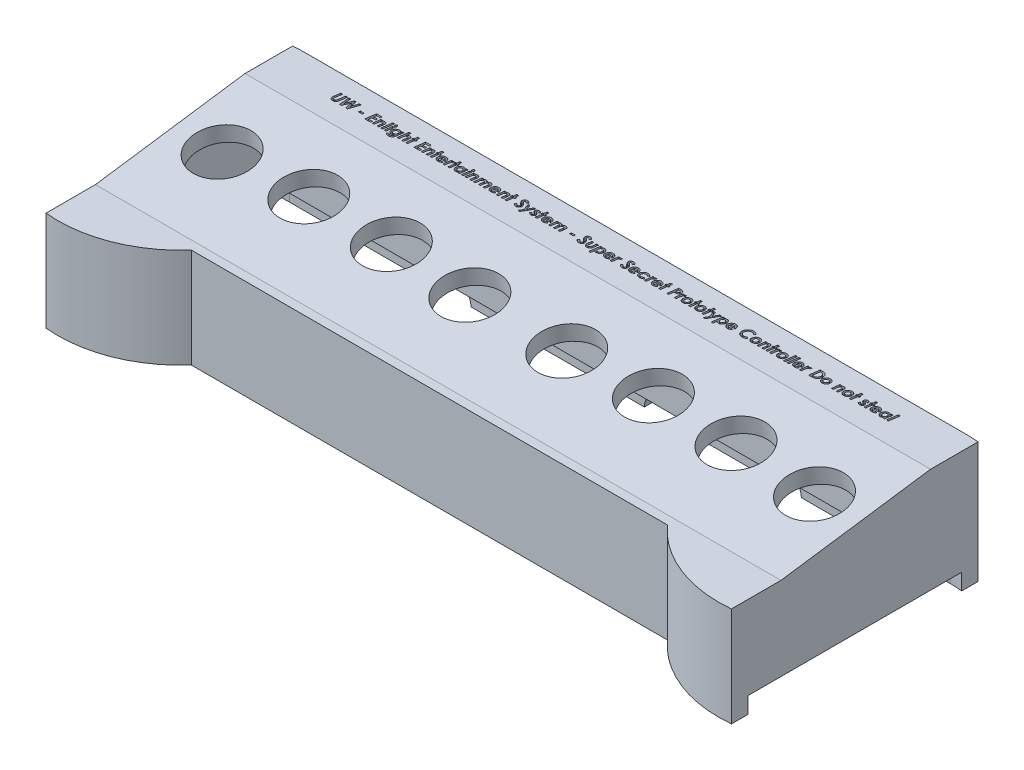
SolidWorks part; units mm, degrees
ref_plane "Front Plane" through (0, 0, 0) normal (0, 0, 1) x (1, 0, 0)
ref_plane "Top Plane" through (0, 0, 0) normal (0, 1, 0) x (1, 0, 0)
ref_plane "Right Plane" through (0, 0, 0) normal (1, 0, 0) x (0, 0, -1)
sketch "Sketch1" plane through (0, 0, 0) normal (0, 1, 0) x (1, 0, 0)
  line L3 (161.7, 30.2918) -> (-41.5, 30.2918)
  line L7 (-13.1019, -33.2082) -> (133.3019, -33.2082)
  line L8 (-63.3461, -39.0229) -> (-76.3578, -44.5347) construction
  line L9 (-41.5, -7.8082) -> (-79.6, -7.8082) construction
  line L10 (161.7, -7.8082) -> (199.8, -7.8082) construction
  arc A0 (-41.5, 30.2918) -> (-13.1019, -33.2082) centre (-41.5, -7.8082) ccw
  arc A1 (133.3019, -33.2082) -> (161.7, 30.2918) centre (161.7, -7.8082) ccw
  point P0 (0, 0)
  dimension "D4" = 76.2
  dimension "D2" = 203.2
  dimension "D1" = 38.1
  dimension "D3" = 63.5
extrude "Boss-Extrude1" add sketch "Sketch1" along normal blind 40.4
sketch "Sketch3" plane through (0, 0, 0) normal (1, 0, 0) x (0, 0, -1)
  line L2 (30.2918, 37.2179) -> (15.5, 37.2179)
  line L3 (30.2918, 40.4) -> (30.2918, 0) construction
  line L10 (55, 0) -> (-55, 0) construction
  line L14 (-30.5, 56.6478) -> (30.2918, 56.6478)
  line L15 (30.2918, 56.6478) -> (30.2918, 37.2179)
  line L18 (-56.0906, 56.6478) -> (-30.5, 56.6478)
  line L19 (15.5, 37.2179) -> (-30.5, 30.6308)
  line L20 (-30.5, 30.6308) -> (-56.0906, 30.6308)
  line L21 (-56.0906, 56.6478) -> (-56.0906, 30.6308)
  dimension "D1" = 37.2179
extrude "Cut-Extrude2" cut sketch "Sketch3" along normal through all both and the other way through all
sketch "Sketch2" plane through (0, 0, 0) normal (0, 1, 0) x (1, 0, 0)
  line L6 (161.7, 25.2918) -> (-41.5, 25.2918)
  line L7 (-15.4337, -28.2082) -> (135.6337, -28.2082)
  line L8 (161.7, 25.2918) -> (-41.5, 25.2918)
  line L9 (-15.4337, -28.2082) -> (135.6337, -28.2082)
  arc A8 (135.6337, -28.2082) -> (161.7, 25.2918) centre (161.7, -7.8082) ccw
  arc A9 (-41.5, 25.2918) -> (-15.4337, -28.2082) centre (-41.5, -7.8082) ccw
  arc A10 (135.6337, -28.2082) -> (161.7, 25.2918) centre (161.7, -7.8082) ccw
  arc A11 (-41.5, 25.2918) -> (-15.4337, -28.2082) centre (-41.5, -7.8082) ccw
  dimension "D1" = 5
extrude "Cut-Extrude3" cut sketch "Sketch2" along normal blind 5
sketch "Sketch4" plane through (0, 0, 0) normal (1, 0, 0) x (0, 0, -1)
  line L1 (22.6718, 32.1379) -> (15.5, 32.1379)
  line L4 (30.2918, 37.2179) -> (15.5, 37.2179) construction
  line L6 (22.6718, 5) -> (22.6718, 32.1379)
  line L7 (22.6718, 5) -> (-29.6351, 5)
  line L8 (15.5, 32.1379) -> (-29.6351, 25.5138)
  line L9 (15.5, 37.2179) -> (-30.5, 30.6308) construction
  line L11 (30.2918, 37.2179) -> (30.2918, 0) construction
  line L13 (-29.6351, 25.5138) -> (-29.6351, 5)
  dimension "D1" = 5.08
  dimension "D2" = 0.2
  dimension "D4" = 7.62
extrude "Cut-Extrude4" cut sketch "Sketch4" along normal blind 161.314 and the other way blind 41.32
sketch "Sketch5" plane through (0, 0, -30.2918) normal (0, 0, -1) x (-1, 0, 0)
  line L1 (41.91, 0) -> (-41.91, 0) construction
  line L5 (-161.7, 37.2179) -> (-161.7, 0) construction
  line L6 (41.5, 37.2179) -> (41.5, 0) construction
  circle A3 centre (-110.9, 0) radius 5.08
  circle A4 centre (-72.8, 0) radius 5.08
  circle A5 centre (-9.3, 0) radius 5.08
  point P10 (-161.7, 18.6089)
  dimension "D1" = 50.8
  dimension "D2" = 50.8
  dimension "D3" = 38.1
  dimension "D4" = 63.5
extrude "Cut-Extrude5" cut sketch "Sketch5" against normal blind 7.62
sketch "Sketch6" plane through (0, 37.2179, 0) normal (0, 1, 0) x (1, 0, 0)
  text T0 "<b><i>UW - Enlight Entertainment System - Super Secret Prototype Controller Do not steal</i></b>"
  dimension "D1" = 45.72
extrude "Cut-Extrude6" cut sketch "Sketch6" against normal blind 1.27
sketch "Sketch9" plane through (0, 34.2951, 4.911) normal (0, 0.9899, 0.1418) x (1, 0, 0)
  line L0 (191.8386, 20.6192) -> (-71.6386, 20.6192) construction
  circle A0 centre (125.7986, 0.2992) radius 8.9662
  circle A1 centre (151.1986, -0.9708) radius 8.9662
  circle A2 centre (74.9986, -0.9708) radius 8.9662
  circle A3 centre (100.3986, 0.2992) radius 8.9662
  circle A4 centre (-5.5986, 0.2992) radius 8.9662
  circle A5 centre (45.2014, -0.9708) radius 8.9662
  circle A6 centre (-30.9986, -0.9708) radius 8.9662
  circle A7 centre (19.8014, 0.2992) radius 8.9662
  dimension "D1" = 17.9324
  dimension "D10" = 17.9324
  dimension "D11" = 17.9324
  dimension "D12" = 17.9324
  dimension "D13" = 17.9324
  dimension "D14" = 17.9324
  dimension "D7" = 17.9324
  dimension "D15" = 17.9324
  dimension "D3" = 25.4
  dimension "D4" = 25.4
  dimension "D5" = 25.4
  dimension "D6" = 25.4
  dimension "D8" = 25.4
  dimension "D9" = 25.4
  dimension "D16" = 40.64
  dimension "D17" = 40.64
  dimension "D18" = 21.59
  dimension "D19" = 20.32
  dimension "D20" = 20.32
  dimension "D21" = 21.59
  dimension "D22" = 21.59
  dimension "D23" = 20.32
  dimension "D24" = 20.32
  dimension "D25" = 21.59
extrude "Cut-Extrude8" cut sketch "Sketch9" against normal blind 50.8
sketch "Sketch10" plane through (0, 0, 0) normal (0, 1, 0) x (1, 0, 0)
  line L0 (-45.31, 31.676) -> (-45.31, -49.5124)
  line L1 (-45.31, 31.676) -> (-97.3213, 31.676)
  line L2 (-97.3213, 31.676) -> (-97.3213, -49.5124)
  line L3 (-97.3213, -49.5124) -> (-45.31, -49.5124)
  line L4 (165.51, 31.676) -> (165.51, -49.5124)
  line L5 (165.51, -49.5124) -> (206.7385, -49.5124)
  line L6 (206.7385, -49.5124) -> (206.7385, 31.676)
  line L7 (206.7385, 31.676) -> (165.51, 31.676)
  arc A0 (-71.6386, 15.5) -> (-72.1054, -30.5) centre (-41.5, -7.8082) ccw construction
  arc A1 (192.3054, -30.5) -> (191.8386, 15.5) centre (161.7, -7.8082) ccw construction
  dimension "D1" = 3.81
  dimension "D2" = 210.82
  dimension "D3" = 3.81
extrude "Cut-Extrude9" cut sketch "Sketch10" along normal through all both and the other way through all
